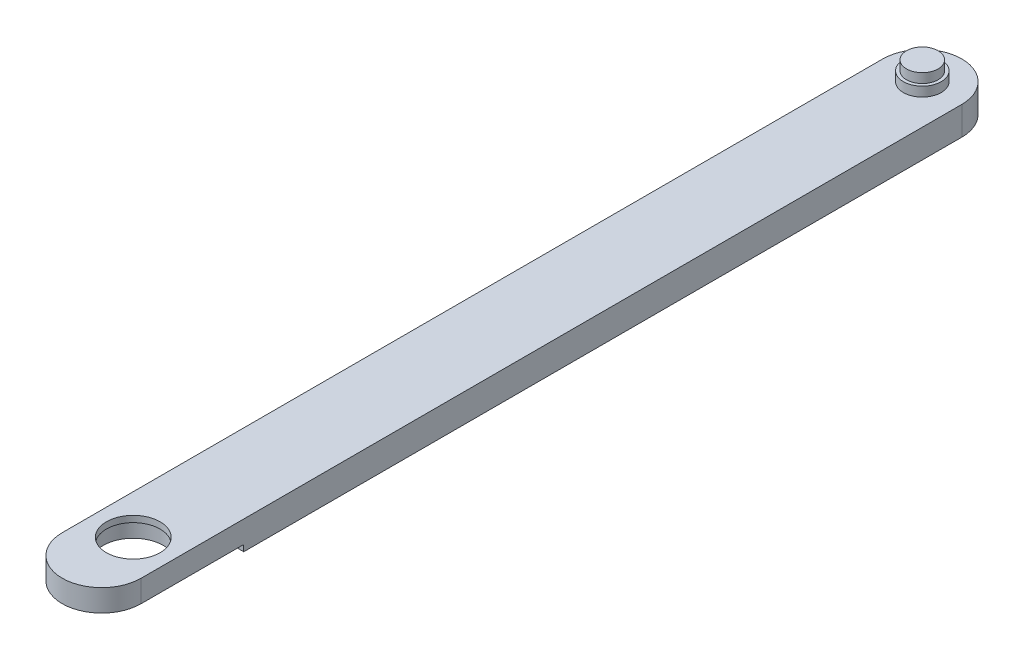
SolidWorks part; units mm, degrees
ref_plane "정면" through (0, 0, 0) normal (0, 0, 1) x (1, 0, 0)
ref_plane "윗면" through (0, 0, 0) normal (0, 1, 0) x (1, 0, 0)
ref_plane "우측면" through (0, 0, 0) normal (1, 0, 0) x (0, 0, -1)
sketch "스케치1" plane through (0, 0, 0) normal (0, 1, 0) x (1, 0, 0)
  circle A0 centre (0, 0) radius 5
  dimension "D1" = 10
extrude "보스-돌출1" add sketch "스케치1" along normal blind 10.5 and the other way blind 10.5
sketch "스케치6" plane through (0, 0, 0) normal (0, 1, 0) x (1, 0, 0)
  line L0 (-12.5, 0) -> (-12.5, -260)
  line L1 (0, 0) -> (0, -260) construction
  line L2 (12.5, 0) -> (12.5, -260)
  arc A0 (12.5, 0) -> (-12.5, 0) centre (0, 0) ccw
  arc A1 (-12.5, -260) -> (12.5, -260) centre (0, -260) ccw
  point P3 (0, 0)
  point P7 (0, 0)
  dimension "D1" = 25
  dimension "D3" = 25
  dimension "D2" = 260
extrude "보스-돌출3" add sketch "스케치6" along normal blind 4.5 and the other way blind 4.5
sketch "스케치7" plane through (0, -4.5, 0) normal (0, -1, 0) x (1, 0, 0)
  circle A0 centre (0, 0) radius 6
  dimension "D1" = 12
extrude "보스-돌출4" add sketch "스케치7" along normal blind 3
sketch "스케치8" plane through (0, 4.5, 0) normal (0, 1, 0) x (1, 0, 0)
  circle A0 centre (0, 0) radius 6
  dimension "D1" = 12
extrude "보스-돌출5" add sketch "스케치8" along normal blind 3
sketch "스케치9" plane through (0, -4.5, 0) normal (0, -1, 0) x (1, 0, 0)
  circle A0 centre (0, 250) radius 9.5
  point P3 (0, 0)
  dimension "D1" = 19
  dimension "D2" = 250
extrude "컷-돌출1" cut sketch "스케치9" against normal blind 7
sketch "스케치10" plane through (0, 2.5, 0) normal (0, -1, 0) x (1, 0, 0)
  circle A0 centre (0, 250) radius 8.5
  dimension "D1" = 17
  dimension "D2" = 250
extrude "컷-돌출2" cut sketch "스케치10" against normal through all
sketch "스케치13" plane through (0, -4.5, 0) normal (0, -1, 0) x (1, 0, 0)
  line L0 (-12.5, 0) -> (-12.5, 260) construction
  line L5 (-12.5, 227.5) -> (12.5, 227.5)
  line L6 (-12.5, 227.5) -> (-12.5, 272.5)
  line L7 (-12.5, 272.5) -> (12.5, 272.5)
  line L8 (12.5, 227.5) -> (12.5, 272.5)
  arc A0 (12.5, 260) -> (-12.5, 260) centre (0, 260) ccw construction
  point P0 (0, 250)
  dimension "D1" = 45
extrude "컷-돌출3" cut sketch "스케치13" against normal blind 2
